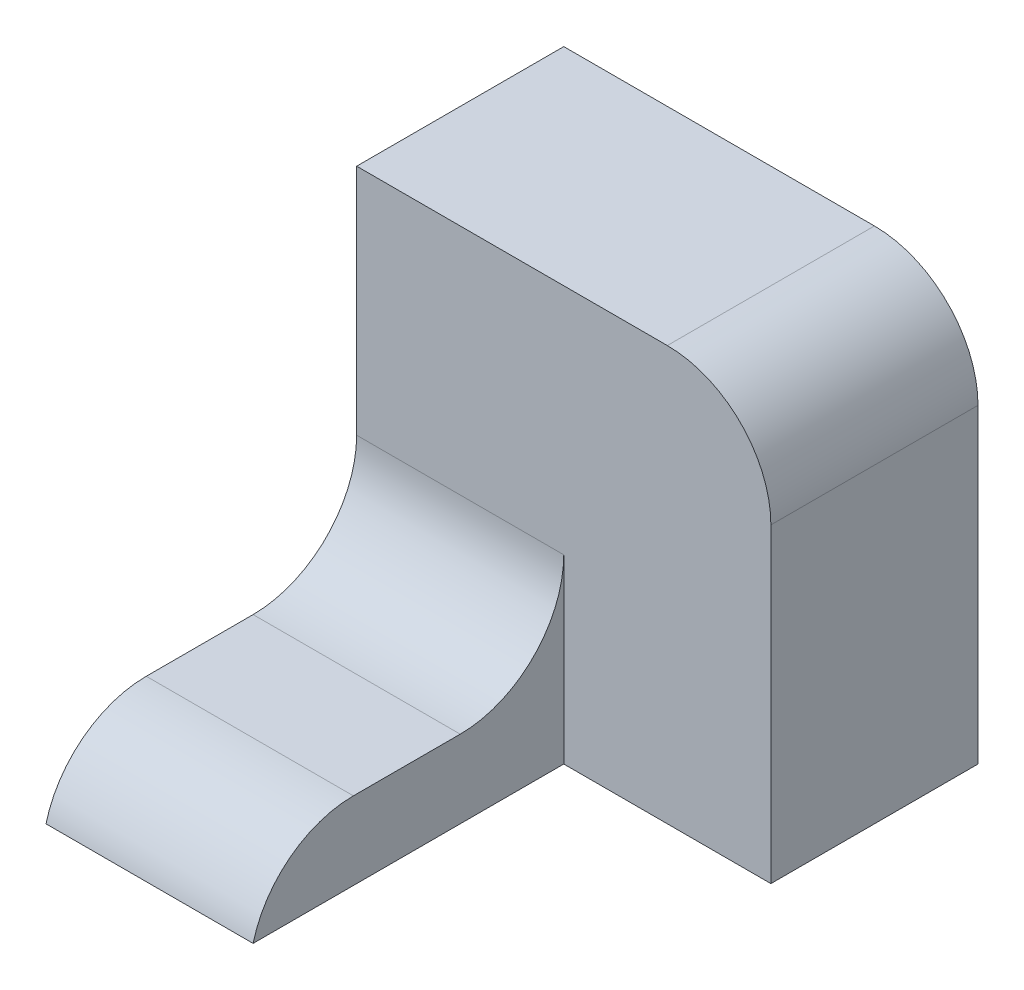
SolidWorks part; units mm, degrees
ref_plane "Front Plane" through (0, 0, 0) normal (0, 0, 1) x (1, 0, 0)
ref_plane "Top Plane" through (0, 0, 0) normal (0, 1, 0) x (1, 0, 0)
ref_plane "Right Plane" through (0, 0, 0) normal (1, 0, 0) x (0, 0, -1)
sketch "Sketch1" plane through (0, 0, 0) normal (0, 0, 1) x (1, 0, 0)
  line L1 (-30, -7.5) -> (-10, -7.5)
  line L2 (-10, -7.5) -> (-10, 0)
  line L3 (-10, 0) -> (-30, 0)
  line L4 (-30, 0) -> (-30, -7.5)
  dimension "D1" = 20
  dimension "Width" = 7.5
extrude "Boss-Extrude1" add sketch "Sketch1" along normal blind 30
sketch "Sketch2" plane through (0, 0, 0) normal (0, 0, 1) x (1, 0, 0)
  line L1 (-30, -7.5) -> (10, -7.5)
  line L2 (10, -7.5) -> (10, 32.5)
  line L3 (10, 32.5) -> (-30, 32.5)
  line L4 (-30, 32.5) -> (-30, -7.5)
  dimension "D1" = 40
  dimension "Width" = 40
extrude "Boss-Extrude2" add sketch "Sketch2" against normal blind 20
fillet "Fillet1" radius 10 3 edges at (-20, 0, 0) (10, 32.5, -10) (-20, 0, 30)
